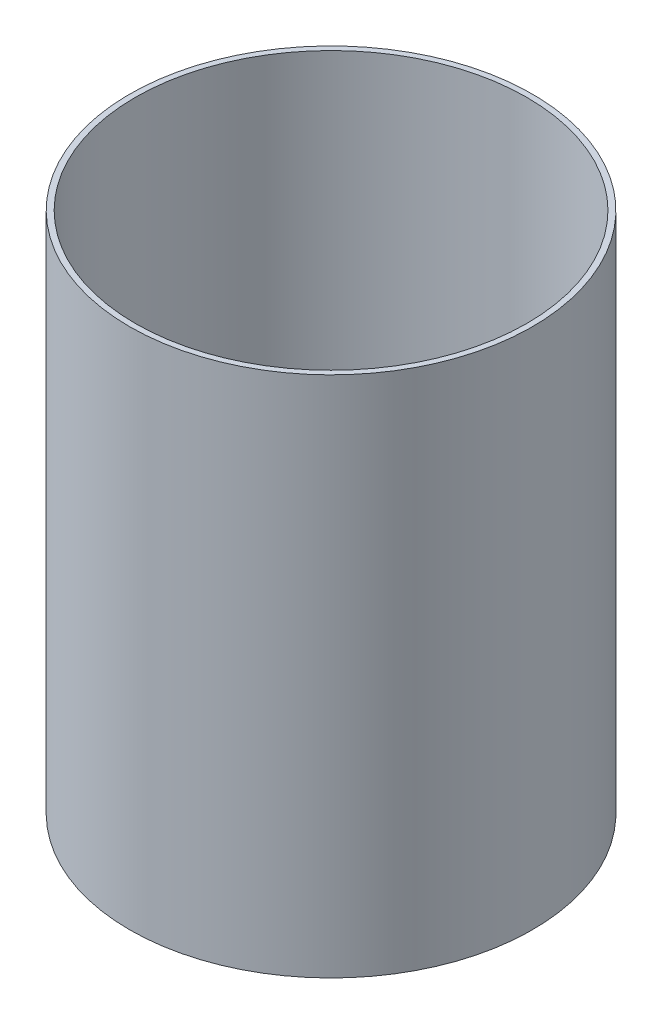
SolidWorks part; units mm, degrees
material "A-Glass Fiber"
ref_plane "Front Plane" through (0, 0, 0) normal (0, 0, 1) x (1, 0, 0)
ref_plane "Top Plane" through (0, 0, 0) normal (0, 1, 0) x (1, 0, 0)
ref_plane "Right Plane" through (0, 0, 0) normal (1, 0, 0) x (0, 0, -1)
sketch "Sketch1" plane through (0, 0, 0) normal (0, 1, 0) x (1, 0, 0)
  circle A0 centre (0, 0) radius 76.1746
  circle A1 centre (0, 0) radius 78.359
  dimension "D1" = 152.3492
  dimension "D2" = 156.718
extrude "Boss-Extrude1" add sketch "Sketch1" along normal blind 203.2
equation "\"Mid_Tube_Length\" = 8in"
equation "\"D1@Boss-Extrude1\"=\"Mid_Tube_Length\""
equation "\"Bodytube_OD\" = 6.17in"
equation "\"Bodytube_ID\" = 5.998in"
equation "\"D1@Sketch1\"=\"Bodytube_ID\""
equation "\"D2@Sketch1\"=\"Bodytube_OD\""
